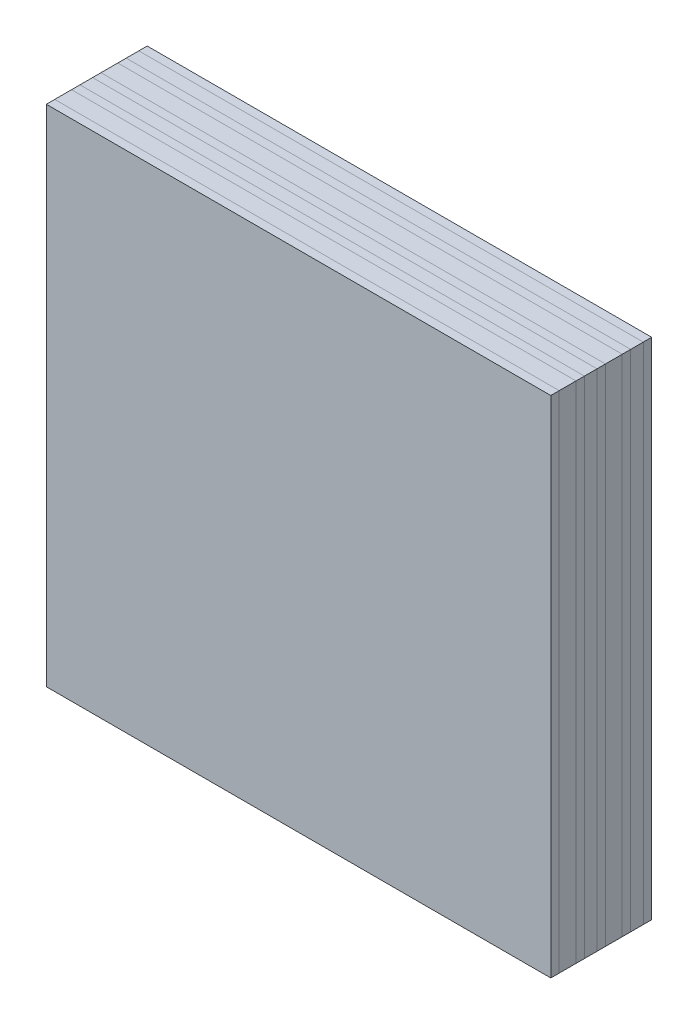
SolidWorks part; units mm, degrees
ref_plane "Front Plane" through (0, 0, 0) normal (0, 0, 1) x (1, 0, 0)
ref_plane "Top Plane" through (0, 0, 0) normal (0, 1, 0) x (1, 0, 0)
ref_plane "Right Plane" through (0, 0, 0) normal (1, 0, 0) x (0, 0, -1)
sketch "Sketch_LayerOutline" plane through (0, 0, 0) normal (0, 0, 1) x (1, 0, 0)
  line L1 (-30, -30) -> (30, -30)
  line L2 (-30, -30) -> (-30, 30)
  line L3 (-30, 30) -> (30, 30)
  line L4 (30, -30) -> (30, 30)
  dimension "D1" = 60
  dimension "D2" = 30
  dimension "D3" = 30
extrude "Layer1" add sketch "Sketch_LayerOutline" along normal blind 1 separate body
extrude "Layer2" add sketch "Sketch_LayerOutline<2>" along normal blind 1.5 from offset 1 separate body
sketch "Sketch_LayerOutline<2>" plane through (0, 0, 0) normal (0, 0, 1) x (1, 0, 0) same geometry as "Sketch_LayerOutline"
extrude "Layer3" add sketch "Sketch_LayerOutline<3>" along normal blind 1 from offset 2.5 separate body
sketch "Sketch_LayerOutline<3>" plane through (0, 0, 0) normal (0, 0, 1) x (1, 0, 0) same geometry as "Sketch_LayerOutline"
extrude "Layer4" add sketch "Sketch_LayerOutline<4>" along normal blind 2 from offset 3.5 separate body
sketch "Sketch_LayerOutline<4>" plane through (0, 0, 0) normal (0, 0, 1) x (1, 0, 0) same geometry as "Sketch_LayerOutline"
extrude "Layer5" add sketch "Sketch_LayerOutline<5>" along normal blind 1 from offset 5.5 separate body
sketch "Sketch_LayerOutline<5>" plane through (0, 0, 0) normal (0, 0, 1) x (1, 0, 0) same geometry as "Sketch_LayerOutline"
extrude "Layer6" add sketch "Sketch_LayerOutline<6>" along normal blind 1.5 from offset 6.5 separate body
sketch "Sketch_LayerOutline<6>" plane through (0, 0, 0) normal (0, 0, 1) x (1, 0, 0) same geometry as "Sketch_LayerOutline"
extrude "Layer7" add sketch "Sketch_LayerOutline<7>" along normal blind 1 from offset 8 separate body
sketch "Sketch_LayerOutline<7>" plane through (0, 0, 0) normal (0, 0, 1) x (1, 0, 0) same geometry as "Sketch_LayerOutline"
extrude "Layer8" add sketch "Sketch_LayerOutline<8>" along normal blind 2 from offset 9 separate body
sketch "Sketch_LayerOutline<8>" plane through (0, 0, 0) normal (0, 0, 1) x (1, 0, 0) same geometry as "Sketch_LayerOutline"
extrude "Layer9" add sketch "Sketch_LayerOutline<9>" along normal blind 1 from offset 11 separate body
sketch "Sketch_LayerOutline<9>" plane through (0, 0, 0) normal (0, 0, 1) x (1, 0, 0) same geometry as "Sketch_LayerOutline"
